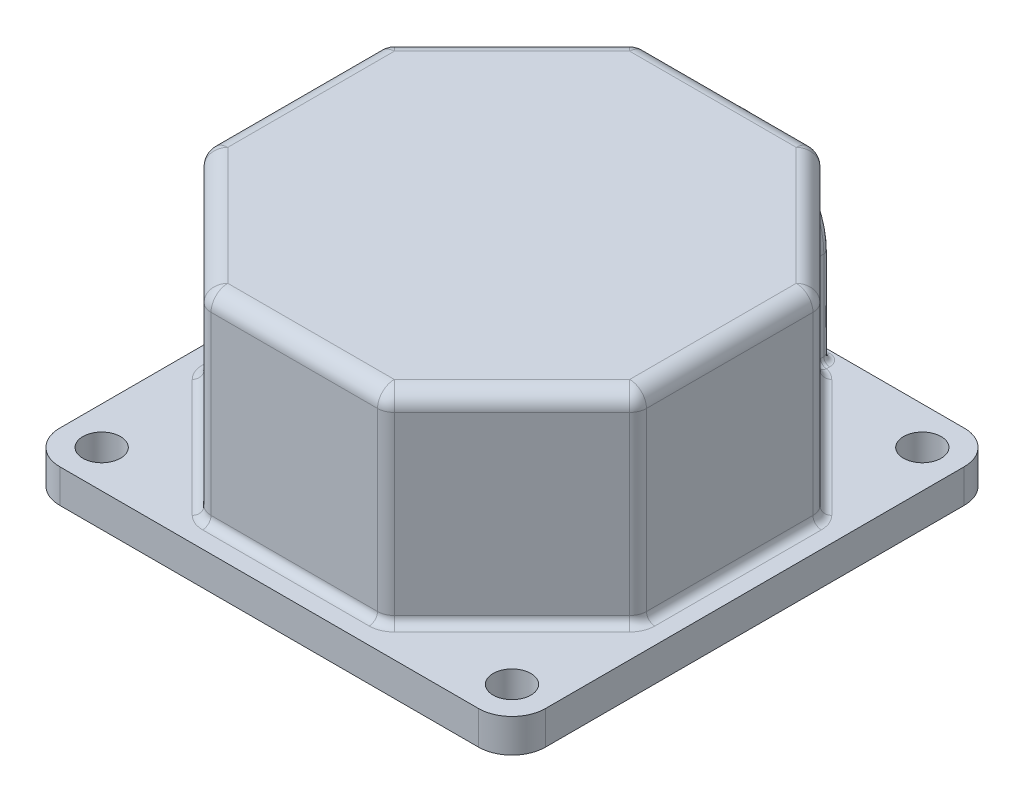
SolidWorks part; units mm, degrees
material "ABS"
ref_plane "Přední rovina" through (0, 0, 0) normal (0, 0, 1) x (1, 0, 0)
ref_plane "Horní rovina" through (0, 0, 0) normal (0, 1, 0) x (1, 0, 0)
ref_plane "Pravá rovina" through (0, 0, 0) normal (1, 0, 0) x (0, 0, -1)
sketch "Skica1" plane through (0, 0, 0) normal (0, 1, 0) x (1, 0, 0)
  line L0 (-29, -29) -> (29, -29)
  line L1 (29, -29) -> (29, 29)
  line L2 (29, 29) -> (-29, 29)
  line L3 (-29, 29) -> (-29, -29)
  line L4 (0, 0) -> (0, 29) construction
  line L5 (0, 0) -> (29, 0) construction
  line L6 (-24.5, -24.5) -> (24.5, -24.5) construction
  line L7 (24.5, -24.5) -> (24.5, 24.5) construction
  line L8 (24.5, 24.5) -> (-24.5, 24.5) construction
  line L9 (-24.5, 24.5) -> (-24.5, -24.5) construction
  line L10 (0, 0) -> (0, -24.5) construction
  line L11 (0, 0) -> (-24.5, 0) construction
  dimension "D1" = 58
  dimension "D2" = 58
extrude "Přidat vysunutím1" add sketch "Skica1" along normal blind 4
sketch "Skica3" plane through (0, 4, 0) normal (0, 1, 0) x (1, 0, 0)
  line L0 (10.7696, -26) -> (26, -10.7696)
  line L1 (26, -10.7696) -> (26, 10.7696)
  line L2 (26, 10.7696) -> (10.7696, 26)
  line L3 (10.7696, 26) -> (-10.7696, 26)
  line L4 (-10.7696, 26) -> (-26, 10.7696)
  line L5 (-26, 10.7696) -> (-26, -10.7696)
  line L6 (-26, -10.7696) -> (-10.7696, -26)
  line L7 (-10.7696, -26) -> (10.7696, -26)
  circle A0 centre (0, 0) radius 26 construction
extrude "Přidat vysunutím2" add sketch "Skica3" along normal blind 24
sketch "Skica4" plane through (0, 0, 0) normal (0, -1, 0) x (1, 0, 0)
  line L1 (9.9411, -24) -> (24, -9.9411)
  line L2 (24, -9.9411) -> (24, 9.9411)
  line L3 (24, 9.9411) -> (9.9411, 24)
  line L4 (9.9411, 24) -> (-9.9411, 24)
  line L5 (-9.9411, 24) -> (-24, 9.9411)
  line L6 (-24, 9.9411) -> (-24, -9.9411)
  line L7 (-24, -9.9411) -> (-9.9411, -24)
  line L8 (-9.9411, -24) -> (9.9411, -24)
  circle A0 centre (0, 0) radius 24 construction
sketch "Skica5" plane through (0, 0, 0) normal (0, -1, 0) x (1, 0, 0)
  line L0 (9.9411, -24) -> (24, -9.9411)
  line L1 (24, -9.9411) -> (24, 9.9411)
  line L2 (24, 9.9411) -> (9.9411, 24)
  line L3 (9.9411, 24) -> (-9.9411, 24)
  line L4 (-9.9411, 24) -> (-24, 9.9411)
  line L5 (-24, 9.9411) -> (-24, -9.9411)
  line L6 (-24, -9.9411) -> (-9.9411, -24)
  line L7 (-9.9411, -24) -> (9.9411, -24)
extrude "Odebrat vysunutím1" cut sketch "Skica5" against normal blind 26
fillet "Zaoblit1" radius 2 16 edges at (-18.3848, 28, 18.3848) (-26, 28, 0) (-18.3848, 28, -18.3848) (0, 28, -26) (18.3848, 28, -18.3848) (26, 28, 0) (18.3848, 28, 18.3848) (0, 28, 26) (-26, 16, 10.7696) (-26, 16, -10.7696) (-10.7696, 16, -26) (10.7696, 16, -26) (26, 16, -10.7696) (26, 16, 10.7696) (10.7696, 16, 26) (-10.7696, 16, 26)
fillet "Zaoblit3" radius 1 40 edges at (0, 0, 24) (-24, 0, 0) (-9.9411, 13, 24) (-16.9706, 26, 16.9706) (-24, 13, 9.9411) (-16.9706, 0, 16.9706) (0, 4, -26) (-18.3848, 4, -18.3848) (-26, 4, 0) (-18.3848, 4, 18.3848) (0, 4, 26) (18.3848, 4, 18.3848) (26, 4, 0) (16.9706, 0, 16.9706) (24, 0, 0) (16.9706, 0, -16.9706) (18.3848, 4, -18.3848) (0, 0, -24) (-16.9706, 0, -16.9706) (-16.9706, 26, -16.9706) (-24, 26, 0) (0, 26, 24) (16.9706, 26, 16.9706) (24, 26, 0) (16.9706, 26, -16.9706) (0, 26, -24) (9.9411, 13, -24) (-9.9411, 13, -24) (-24, 13, -9.9411) (9.9411, 13, 24) (24, 13, -9.9411) (24, 13, 9.9411) (25.8478, 4, -10.7065) (25.8478, 4, 10.7065) (10.7065, 4, 25.8478) (-10.7065, 4, 25.8478) (-25.8478, 4, 10.7065) (-25.8478, 4, -10.7065) (-10.7065, 4, -25.8478) (10.7065, 4, -25.8478)
fillet "Zaoblit4" radius 4 4 edges at (-29, 2, 29) (29, 2, 29) (-29, 2, -29) (29, 2, -29)
hole_wizard "M4 díra s vůlí1" positions "Skica7" profile "Skica6" hole size "M4" standard "ANSI Metric"
sketch "Skica7" plane through (0, 0, 0) normal (0, -1, 0) x (-1, 0, 0)
  point P0 (24.5, -24.5)
sketch "Skica6" plane through (-24.5, 0, 24.5) normal (1, 0, 0) x (0, 0, -1)
  line L0 (0, 0) -> (0, 26.3519)
  line L1 (0, 26.3519) -> (2.25, 25)
  line L2 (2.25, 25) -> (2.25, 0)
  line L5 (2.25, 0) -> (0, 0)
  line L10 (0, 26.3519) -> (-2.25, 25) construction
  line L11 (0, -6.35) -> (0, 107.95) construction
  dimension "Průměr díry" = 4.5
  dimension "Hloubka díry" = 25
  dimension "Úhel vrtání" = 118
pattern_linear "LinPole1" count 2 spacing 49 along (1, 0, 0) count 2 spacing 49 along (0, 0, -1) of "M4 díra s vůlí1"
sketch "Skica8" plane through (0, 0, -26) normal (0, 0, -1) x (-1, 0, 0)
  line L0 (0.1496, 25.2607) -> (-0.1496, 25.2607)
  line L1 (-9.9411, 15.3207) -> (-9.9411, 4)
  line L2 (-9.9411, 4) -> (9.9411, 4)
  line L3 (9.9411, 4) -> (9.9411, 15.3207)
  line L4 (0, 0) -> (0, 26) construction
  line L5 (9.9411, 26) -> (-9.9411, 26) construction
  line L6 (-9.9411, 26) -> (-9.9411, 5) construction
  line L7 (9.9411, 5) -> (9.9411, 26) construction
  line L8 (-25, 4) -> (25, 4) construction
  line L9 (-9.9411, 15.3207) -> (9.15, 15.3207) construction
  circle A0 centre (0, 15.3207) radius 9.15 construction
  arc A1 (-9.9411, 15.3207) -> (9.9411, 15.3207) centre (0, 15.3207) cw
  dimension "D1" = 9.94
extrude "Přidat vysunutím3" add sketch "Skica8" along normal blind 2 contours L1 L2 L3 A1
sketch "Skica14" plane through (0, 0, -28) normal (0, 0, -1) x (-1, 0, 0)
  circle A0 centre (0, 15.3207) radius 6.6
sketch "Skica15" plane through (0, 0, -28) normal (0, 0, -1) x (-1, 0, 0)
  circle A0 centre (0, 15.3207) radius 6.6
extrude "Odebrat vysunutím2" cut sketch "Skica15" against normal up to surface (4 mm away) up to face at (0, 13, -24)
fillet "Zaoblit5" radius 0.7 11 edges at (0, 4, -28) (9.9411, 4, -27.5) (9.9411, 4.2929, -26.2929) (9.9411, 10.1604, -26) (-9.9411, 4, -27.5) (-9.9411, 4.2929, -26.2929) (-9.9411, 10.1604, -26) (9.9411, 9.6604, -28) (-9.9411, 9.6604, -28) (0, 25.2618, -26) (0, 25.2618, -28)
